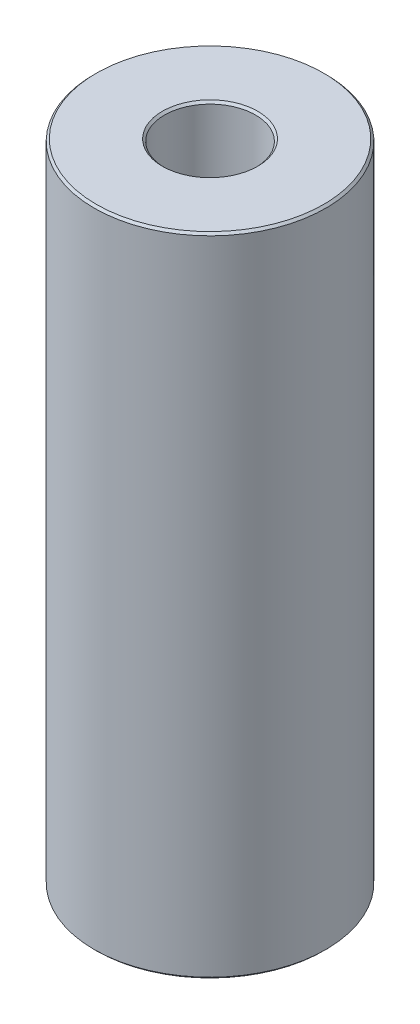
SolidWorks part; units mm, degrees
ref_plane "Front Plane" through (0, 0, 0) normal (0, 0, 1) x (1, 0, 0)
ref_plane "Top Plane" through (0, 0, 0) normal (0, 1, 0) x (1, 0, 0)
ref_plane "Right Plane" through (0, 0, 0) normal (1, 0, 0) x (0, 0, -1)
sketch "Sketch1" plane through (0, 0, 0) normal (0, 1, 0) x (1, 0, 0)
  circle A0 centre (0, 0) radius 52.5
  dimension "SLEEVE_OD" = 105
extrude "Boss-Extrude1" add sketch "Sketch1" along normal blind 292.9115
sketch "Sketch2" plane through (0, 0, 0) normal (0, 1, 0) x (1, 0, 0)
  circle A0 centre (0, 0) radius 20.6331
  dimension "BORE_D" = 41.2662
extrude "Cut-Extrude1" cut sketch "Sketch2" along normal through all
chamfer "Chamfer1" distance 0.9829 angle 45 4 edges at (0, 292.9115, 20.6331) (0, 0, 20.6331) (0, 0, 52.5) (0, 292.9115, 52.5)
